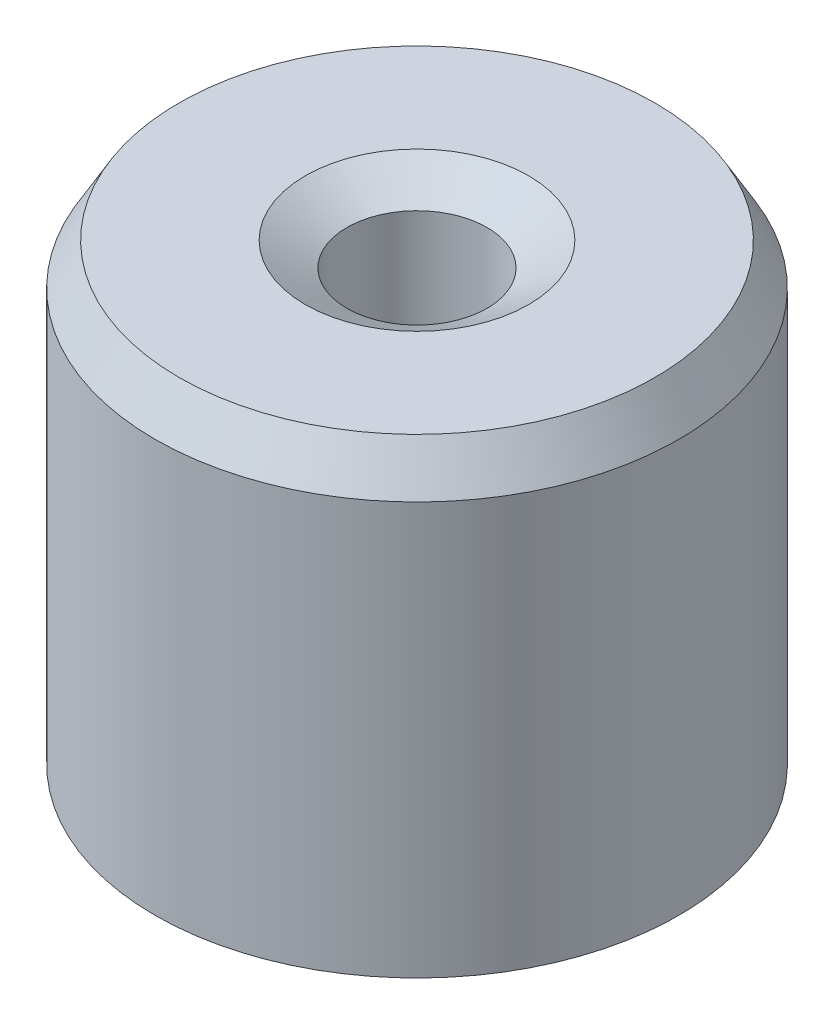
SolidWorks part; units mm, degrees
ref_plane "Front Plane" through (0, 0, 0) normal (0, 0, 1) x (1, 0, 0)
ref_plane "Top Plane" through (0, 0, 0) normal (0, 1, 0) x (1, 0, 0)
ref_plane "Right Plane" through (0, 0, 0) normal (1, 0, 0) x (0, 0, -1)
sketch "Sketch1" plane through (0, 0, 0) normal (0, 1, 0) x (1, 0, 0)
  circle A0 centre (0, 0) radius 5
  dimension "SLEEVE_OD" = 10
extrude "Boss-Extrude1" add sketch "Sketch1" along normal blind 9.1231
sketch "Sketch2" plane through (0, 0, 0) normal (0, 1, 0) x (1, 0, 0)
  circle A0 centre (0, 0) radius 1.338
  dimension "BORE_D" = 2.676
extrude "Cut-Extrude1" cut sketch "Sketch2" along normal through all
chamfer "Chamfer1" distance 0.7938 angle 30 4 edges at (0, 9.1231, 1.338) (0, 0, 1.338) (0, 0, 5) (0, 9.1231, 5) first distance on face at (0, 9.1231, 1.338) first distance on face at (0, 0, 1.338) first distance on face at (0, 9.1231, 5)
